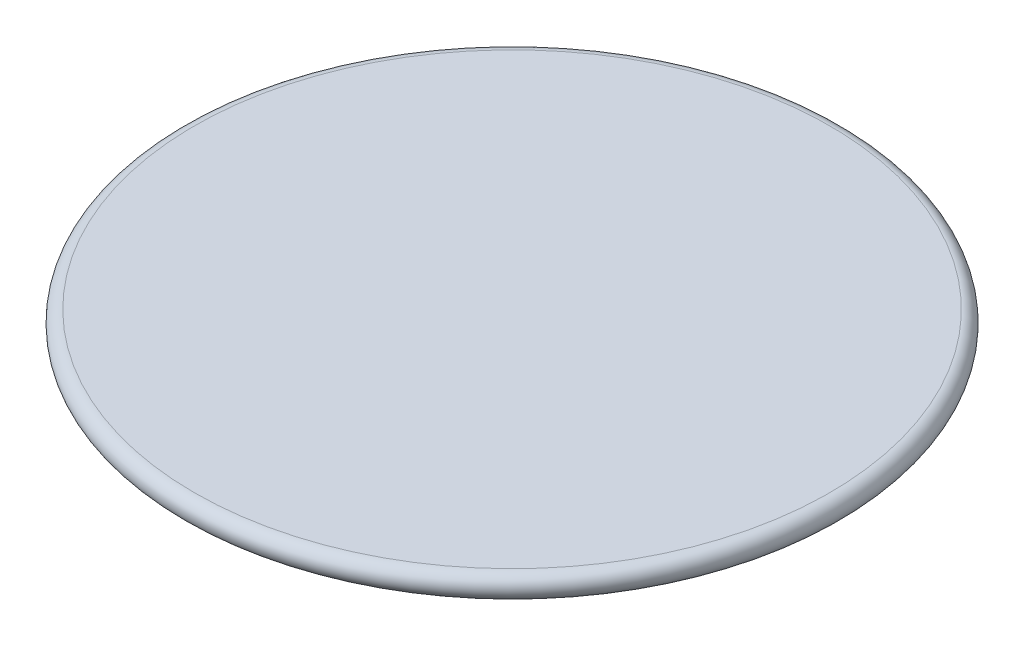
SolidWorks part; units mm, degrees
ref_plane "Front Plane" through (0, 0, 0) normal (0, 0, 1) x (1, 0, 0)
ref_plane "Top Plane" through (0, 0, 0) normal (0, 1, 0) x (1, 0, 0)
ref_plane "Right Plane" through (0, 0, 0) normal (1, 0, 0) x (0, 0, -1)
sketch "Sketch2" plane through (0, 0, 0) normal (0, 1, 0) x (1, 0, 0)
  circle A0 centre (0, 0) radius 22.25
  dimension "D1" = 44.5
extrude "Boss-Extrude1" add sketch "Sketch2" along normal blind 1.6
fillet "Fillet2" 2 edges at (0, 1.6, 22.25) (0, 0, 22.25) type full round first side face at (0, 1.6, 22.25) second side face at (0, 0, 22.25) middle face at (0, 1.6, 22.25)
